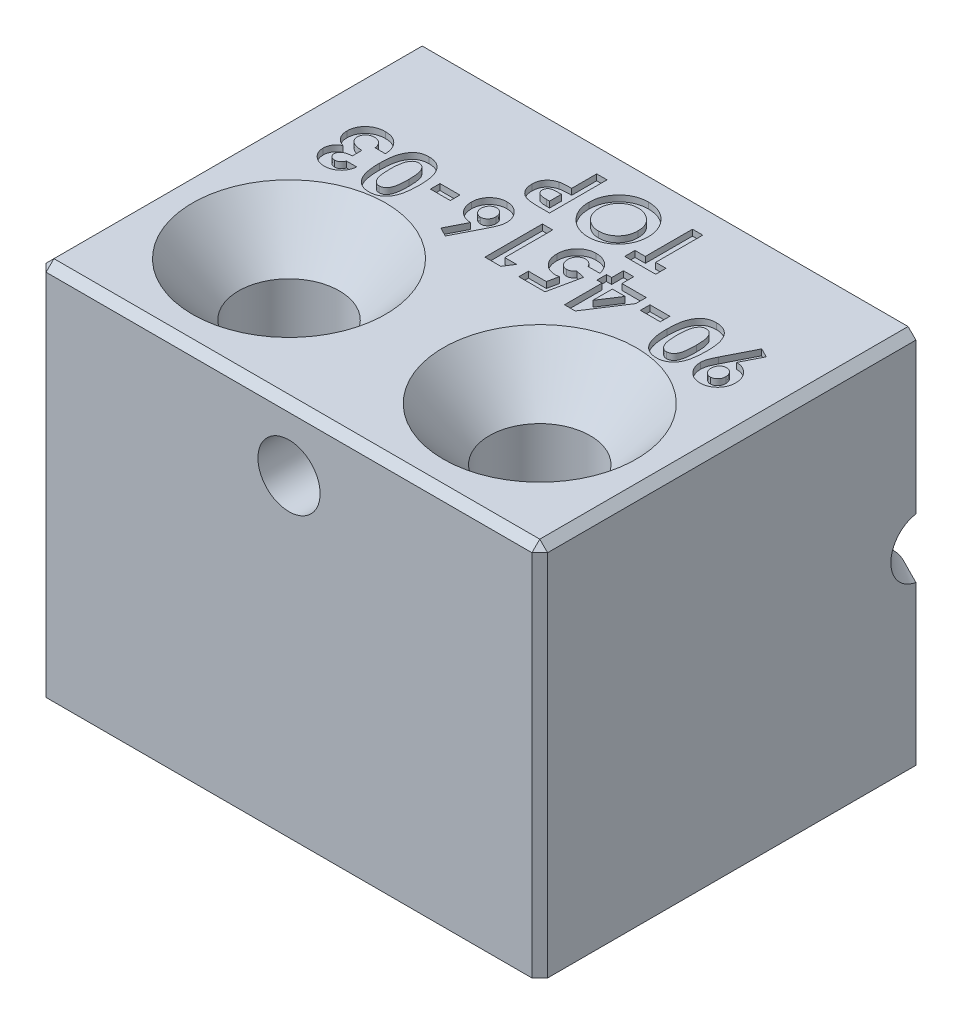
SolidWorks part; units mm, degrees
material "A-2 Steel"
ref_plane "Alzado" through (0, 0, 0) normal (0, 0, 1) x (1, 0, 0)
ref_plane "Planta" through (0, 0, 0) normal (0, 1, 0) x (1, 0, 0)
ref_plane "Vista lateral" through (0, 0, 0) normal (1, 0, 0) x (0, 0, -1)
sketch "Croquis1" plane through (0, 0, 0) normal (0, 1, 0) x (1, 0, 0)
  line L1 (12.7, 9.525) -> (-12.7, 9.525)
  line L2 (12.7, 9.525) -> (12.7, -9.525)
  line L3 (12.7, -9.525) -> (-12.7, -9.525)
  line L4 (-12.7, 9.525) -> (-12.7, -9.525)
  line L5 (0, -9.525) -> (0, 9.525) construction
  line L6 (12.7, 0) -> (-12.7, 0) construction
  point P64 (0, 0)
  dimension "D1" = 19.05
  dimension "D2" = 25.4
extrude "Saliente-Extruir1" add sketch "Croquis1" along normal blind 19.05
sketch "Croquis3" plane through (0, 19.05, 0) normal (0, 1, 0) x (1, 0, 0)
  line L0 (6.35, -3.175) -> (-6.35, -3.175) construction
  line L2 (0, 0) -> (0, -3.175) construction
  line L4 (-12.7, -9.525) -> (12.7, -9.525) construction
  point P0 (-6.35, -3.175)
  point P2 (6.35, -3.175)
  dimension "D1" = 6.35
  dimension "D2" = 12.7
hole_wizard "Avellanado para tornillo con cabeza ovalada de #101" positions "Croquis3" profile "Croquis4" countersink size "#10" standard "Ansi Inch" end condition through all
sketch "Croquis4" plane through (-6.35, 19.05, 3.175) normal (1, 0, 0) x (0, 0, 1)
  line L0 (0, 0) -> (0, 19.05)
  line L1 (0, 19.05) -> (2.5527, 19.05)
  line L2 (2.5527, 19.05) -> (2.5527, 2.6882)
  line L3 (2.5527, 2.6882) -> (4.8895, 0)
  line L5 (4.8895, 0) -> (0, 0)
  line L6 (-2.5527, 2.6882) -> (-4.8895, 0) construction
  line L11 (0, -6.35) -> (0, 107.95) construction
  dimension "Diámetro de taladro hasta el siguiente" = 5.1054
  dimension "Profundidad de taladro hasta el siguiente" = 19.05
  dimension "Diámetro de avellanado cercano" = 9.779
  dimension "Ángulo de avellanado cercano" = 82
sketch "Croquis6" plane through (-12.7, 0, 0) normal (1, 0, 0) x (0, 0, -1)
  line L0 (9.525, 19.05) -> (9.525, 0) construction
  circle A0 centre (9.525, 9.525) radius 7.112
  dimension "D1" = 14.224
extrude "Cortar-Extruir2" cut sketch "Croquis6" along normal blind 6.35 draft 45
sketch "Croquis8" plane through (12.7, 0, 0) normal (1, 0, 0) x (0, 0, -1)
  line L1 (9.779, 9.525) -> (9.525, 9.525) construction
  line L2 (9.525, 19.05) -> (9.525, 0) construction
  circle A0 centre (9.779, 9.525) radius 0.6604
  dimension "D1" = 1.3208
  dimension "D2" = 0.254
extrude "Cortar-Extruir3" cut sketch "Croquis8" against normal through all
fillet "Redondeo1" radius 0.508 2 edges at (3.175, 8.9154, -9.525) (3.175, 10.1346, -9.525)
chamfer "Chaflán3" distance 0.8636 angle 45 1 edges at (12.7, 9.525, -9.1186) tangent propagation no
sketch "Croquis9" plane through (0, 0, 9.525) normal (0, 0, 1) x (1, 0, 0)
  line L0 (0, 19.05) -> (0, 15.875) construction
  line L1 (-12.7, 19.05) -> (12.7, 19.05) construction
  point P0 (0, 15.875)
  dimension "D1" = 3.175
hole_wizard "Taladros de espiga de 1/8 (0.124)2" positions "Croquis9" profile "Croquis10" hole size "1/8" standard "Ansi Inch" end condition through all
sketch "Croquis10" plane through (0, 15.875, 9.525) normal (1, 0, 0) x (0, -1, 0)
  line L0 (0, 0) -> (0, 19.05)
  line L1 (0, 19.05) -> (1.5748, 19.05)
  line L2 (1.5748, 19.05) -> (1.5748, 0)
  line L5 (1.5748, 0) -> (0, 0)
  line L11 (0, -6.35) -> (0, 107.95) construction
  dimension "Diámetro de taladro hasta el siguiente" = 3.1496
  dimension "Profundidad de taladro hasta el siguiente" = 19.05
sketch "Croquis11" plane through (0, 19.05, 0) normal (0, 1, 0) x (1, 0, 0)
  line L0 (12.7, 4.7625) -> (-12.7, 4.7625) construction
  line L1 (5.7224, 8.3344) -> (-5.7224, 8.3344) construction
  line L2 (0, 4.7625) -> (0, 8.3344) construction
  line L4 (0, 0) -> (0, 4.7625) construction
  text T0 "90-4516-03" font "Century Gothic" height in points 11
  text T1 "TOP" font "Century Gothic" height in points 11
  dimension "D1" = 4.7625
  dimension "D2" = 3.5719
  dimension "D3" = 25.4
extrude "Cortar-Extruir4" cut sketch "Croquis11" against normal blind 0.3048
chamfer "Chaflán4" distance 0.3969 angle 45 5 edges at (-12.7, 9.525, 9.525) (12.7, 9.525, 9.525) (12.7, 19.05, 0) (0, 19.05, 9.525) (-12.7, 19.05, 0)
